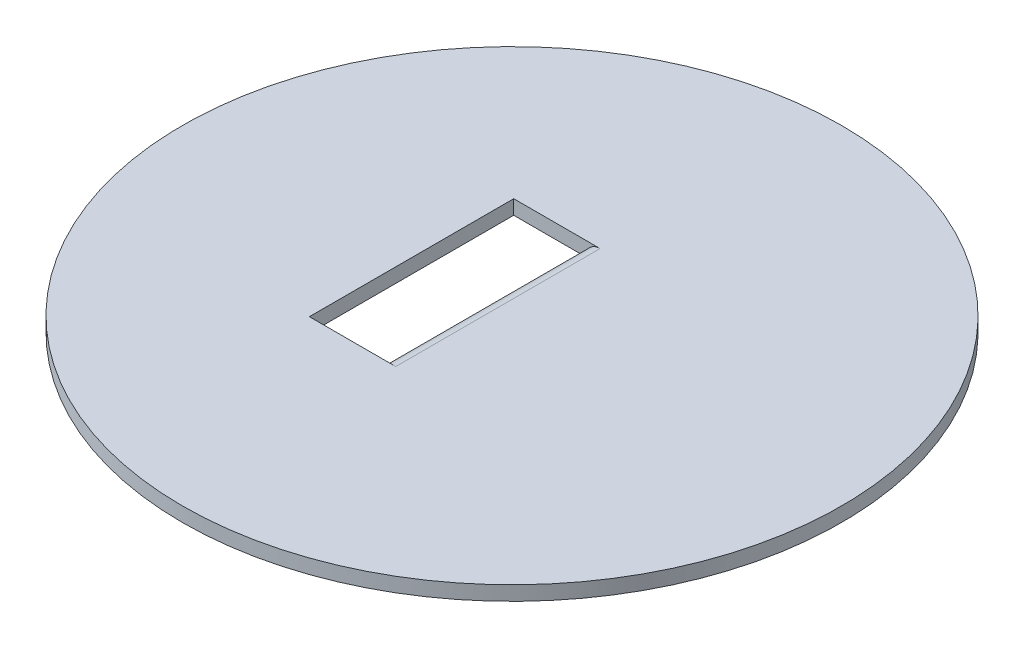
SolidWorks part; units mm, degrees
material "VeroWhite Plus"
ref_plane "Front Plane" through (0, 0, 0) normal (0, 0, 1) x (1, 0, 0)
ref_plane "Top Plane" through (0, 0, 0) normal (0, 1, 0) x (1, 0, 0)
ref_plane "Right Plane" through (0, 0, 0) normal (1, 0, 0) x (0, 0, -1)
sketch "Sketch1" plane through (0, 0, 0) normal (0, 1, 0) x (1, 0, 0)
  line L0 (-21.9089, 7) -> (-2.0805, 7) construction
  line L1 (-2.0805, 7) -> (-2.0805, -7) construction
  line L2 (-2.0805, -7) -> (-21.9089, -7) construction
  line L3 (15, 14.7404) -> (5, 14.7404) construction
  line L4 (15, -14.7404) -> (15, 14.7404) construction
  line L5 (5, -14.7404) -> (15, -14.7404) construction
  line L6 (5, 14.7404) -> (5, -14.7404) construction
  line L7 (-21.7715, 7.1) -> (-1.9805, 7.1)
  line L8 (-1.9805, 7.1) -> (-1.9805, -7.1)
  line L9 (-1.9805, -7.1) -> (-21.7715, -7.1)
  arc A0 (-21.9089, -7) -> (-21.9089, 7) centre (0, 0) ccw construction
  circle A1 centre (-11.6425, 11) radius 2 construction
  circle A2 centre (-11.6425, -11) radius 2 construction
  arc A3 (-21.7715, -7.1) -> (-21.7715, 7.1) centre (0, 0) ccw
  point P13 (-11.6425, -9)
  point P15 (-11.6425, 9)
  dimension "D1" = 2
  dimension "D2" = 2
  dimension "D3" = 5
  dimension "D4" = 0.1
extrude "Boss-Extrude1" add sketch "Sketch1" along normal blind 1
sketch "Sketch2" plane through (0, 0, 0) normal (0, -1, 0) x (1, 0, 0)
  line L0 (15, -14.7404) -> (5, -14.7404) construction
  line L1 (15, 14.7404) -> (15, -14.7404) construction
  line L2 (5, 14.7404) -> (15, 14.7404) construction
  line L3 (5, -14.7404) -> (5, 14.7404) construction
  line L4 (15, -14.7404) -> (5, -14.7404) construction
  line L5 (15, 14.7404) -> (15, -14.7404) construction
  line L6 (5, 14.7404) -> (15, 14.7404) construction
  line L7 (5, -14.7404) -> (5, 14.7404) construction
  line L8 (5.1, -14.6404) -> (5.1, 14.6404)
  line L9 (5.1, 14.6404) -> (14.9, 14.6404)
  line L10 (14.9, 14.6404) -> (14.9, -14.6404)
  line L11 (14.9, -14.6404) -> (5.1, -14.6404)
  circle A0 centre (-11.6425, -11) radius 2 construction
  circle A1 centre (-11.6425, 11) radius 2 construction
  circle A2 centre (-11.6425, -11) radius 2 construction
  circle A3 centre (-11.6425, 11) radius 2 construction
  circle A4 centre (-11.6425, 11) radius 1.9
  circle A5 centre (-11.6425, -11) radius 1.9
  dimension "D1" = 0.1
extrude "Boss-Extrude2" add sketch "Sketch2" along normal blind 0.5
fillet "Fillet1" radius 1 1 edges at (-1.9805, 1, 0)
sketch "Sketch3" plane through (0, 1, 0) normal (0, 1, 0) x (1, 0, 0)
  line L0 (-1.9805, -7.1) -> (-21.7715, -7.1) construction
  line L1 (-21.7715, 7.1) -> (-1.9805, 7.1) construction
  line L2 (-6.9805, -7.1) -> (-21.7715, -7.1)
  line L3 (-21.7715, 7.1) -> (-6.9805, 7.1)
  line L4 (-1.9805, 7.1) -> (-1.9805, -7.1) construction
  line L5 (-6.9805, -7.1) -> (-6.9805, 7.1)
  arc A1 (-21.7715, -7.1) -> (-21.7715, 7.1) centre (0, 0) cw
  dimension "D1" = 5
extrude "Boss-Extrude3" add sketch "Sketch3" against normal up to surface (1 mm away) up to face at (-0.7081, 0, 0)
